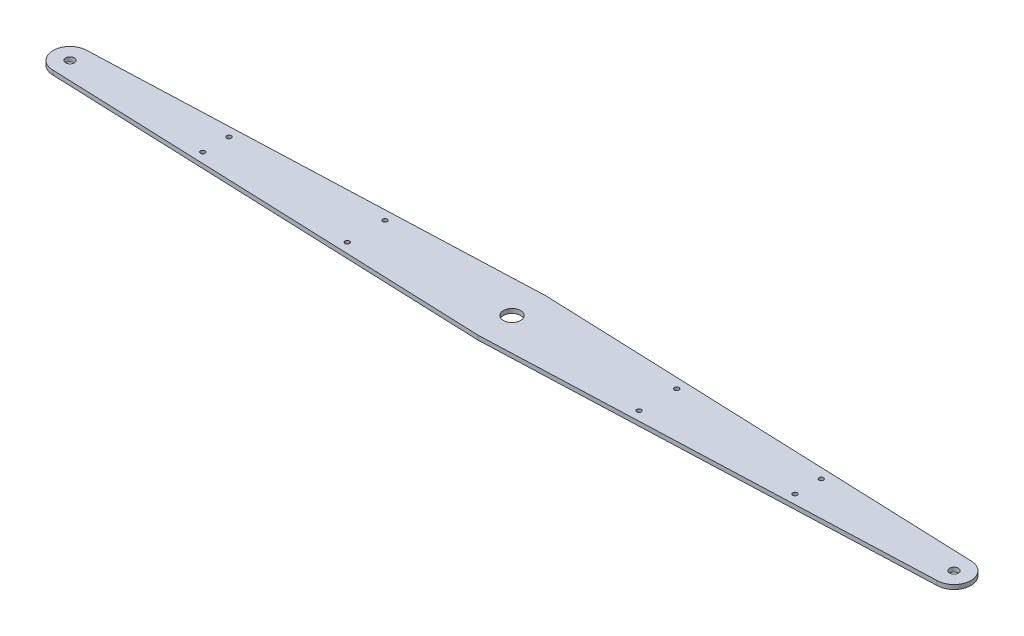
SolidWorks part; units mm, degrees
material "6061-T6 (SS)"
ref_plane "Front Plane" through (0, 0, 0) normal (0, 0, 1) x (1, 0, 0)
ref_plane "Top Plane" through (0, 0, 0) normal (0, 1, 0) x (1, 0, 0)
ref_plane "Right Plane" through (0, 0, 0) normal (1, 0, 0) x (0, 0, -1)
sketch "Sketch2" plane through (0, 0, 0) normal (0, 1, 0) x (1, 0, 0)
  line L0 (0, 0) -> (0, 25) construction
  line L1 (0, 0) -> (0, -25) construction
  line L2 (0, 0) -> (-325, 0) construction
  line L3 (-325, 12.5) -> (0, 25)
  line L4 (-325, -12.5) -> (0, -25)
  line L5 (325, -12.5) -> (0, -25)
  line L6 (325, 12.5) -> (0, 25)
  arc A0 (-325, 12.5) -> (-325, -12.5) centre (-325, 0) ccw
  arc A1 (325, 12.5) -> (325, -12.5) centre (325, 0) cw
  dimension "D2" = 25
  dimension "D1" = 50
  dimension "Half of Chassis Width" = 325
extrude "Boss-Extrude1" add sketch "Sketch2" along normal blind 3.18
sketch "Sketch3" plane through (0, 3.18, 0) normal (0, 1, 0) x (1, 0, 0)
  line L0 (0, 25) -> (0, -25) construction
  line L1 (-325, 0) -> (0, 0) construction
  line L3 (-217.75, 9.625) -> (-217.75, 0) construction
  line L4 (-107.25, -13.875) -> (-107.25, 0) construction
  line L6 (-325, -12.5) -> (0, -25) construction
  line L7 (-217.75, 9.625) -> (-217.75, 16.625) construction
  line L8 (0, 25) -> (-325, 12.5) construction
  line L9 (-107.25, -13.875) -> (-107.25, -20.875) construction
  circle A0 centre (0, 0) radius 6.35
  circle A1 centre (-325, 0) radius 3.175
  circle A3 centre (-217.75, 9.625) radius 1.65
  circle A4 centre (-107.25, -13.875) radius 1.65
  circle A8 centre (325, 0) radius 3.175
  circle A9 centre (-107.25, 13.875) radius 1.65
  circle A10 centre (-217.75, -9.625) radius 1.65
  circle A11 centre (107.25, -13.875) radius 1.65
  circle A12 centre (107.25, 13.875) radius 1.65
  circle A13 centre (217.75, -9.625) radius 1.65
  circle A14 centre (217.75, 9.625) radius 1.65
  dimension "D1" = 12.7
  dimension "D2" = 6.35
  dimension "Hole2" = 217.75
  dimension "Hole1" = 107.25
  dimension "D5" = 7
  dimension "D6" = 7
extrude "Cut-Extrude1" cut sketch "Sketch3" against normal through all
equation "\"Half of Chassis Width@Sketch2\"= \"Chassis Width@Differential System Assy - Option 1.Assembly\" / 2"
equation "\"Hole2@Sketch3\" = \"Chassis Width@Differential System Assy - Option 1.Assembly\" / 2 * 0.67"
equation "\"Hole1@Sketch3\"= \"Chassis Width@Differential System Assy - Option 1.Assembly\" / 2 * 0.33"
